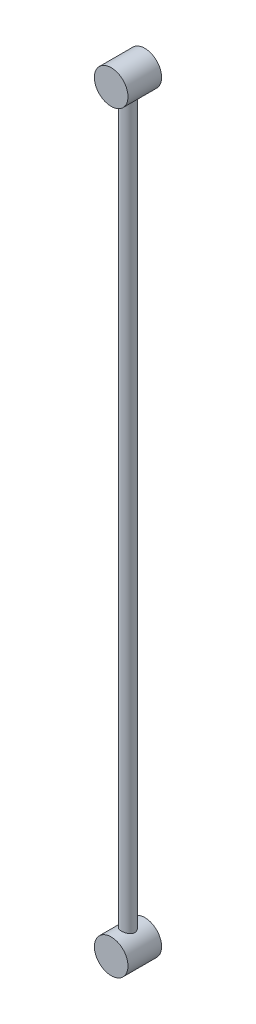
SolidWorks part; units mm, degrees
ref_plane "Front Plane" through (0, 0, 0) normal (0, 0, 1) x (1, 0, 0)
ref_plane "Top Plane" through (0, 0, 0) normal (0, 1, 0) x (1, 0, 0)
ref_plane "Right Plane" through (0, 0, 0) normal (1, 0, 0) x (0, 0, -1)
sketch "Sketch1" plane through (0, 0, 0) normal (1, 0, 0) x (0, 0, -1)
  circle A0 centre (0, 0) radius 5
  dimension "D1" = 10
extrude "Boss-Extrude1" add sketch "Sketch1" along normal blind 80
sketch "Sketch2" plane through (0, 0, 0) normal (0, 0, 1) x (1, 0, 0)
  circle A0 centre (-7.666, 0) radius 10
  dimension "D1" = 20
extrude "Boss-Extrude2" add sketch "Sketch2" along normal blind 10 and the other way blind 10 separate body
sketch "Sketch3" plane through (0, 0, 0) normal (0, 1, 0) x (1, 0, 0)
  line L0 (-7.666, 10) -> (-7.666, -10) construction
  circle A0 centre (-7.666, 0) radius 3.9882
ref_plane "Plane1" through (0, -224, 0) normal (0, 1, 0) x (1, 0, 0)
mirror "Mirror1" about plane through (0, -224, 0) normal (0, 1, 0) of bodies 101 102 103
ref_plane "Plane2" through (40, 0, 0) normal (-1, 0, 0) x (0, 0, 1)
ref_axis "Axis1" through (80, 0, 0) along (-1, 0, 0)
extrude "Boss-Extrude3" add sketch "Sketch3" against normal blind 450
delete or keep bodies "Body-Delete/Keep 1" type delete bodies bodies 101
delete or keep bodies "Body-Delete/Keep 2" type delete bodies bodies 104
